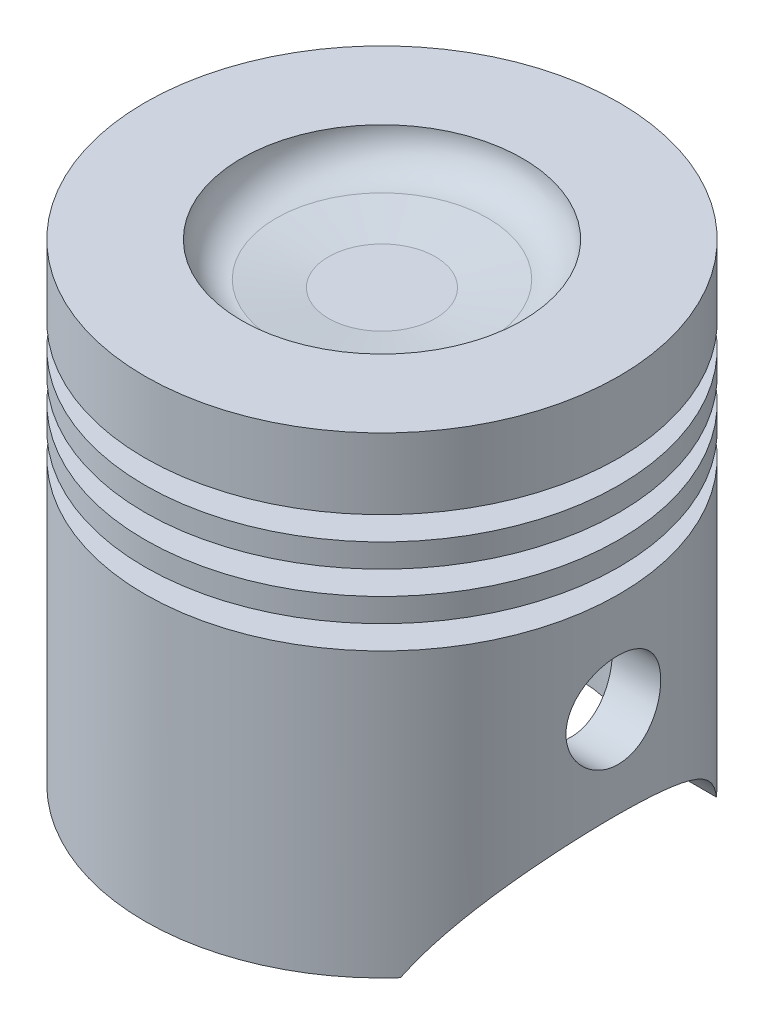
SolidWorks part; units mm, degrees
ref_plane "Front Plane" through (0, 0, 0) normal (0, 0, 1) x (1, 0, 0)
ref_plane "Top Plane" through (0, 0, 0) normal (0, 1, 0) x (1, 0, 0)
ref_plane "Right Plane" through (0, 0, 0) normal (1, 0, 0) x (0, 0, -1)
sketch "Sketch1" plane through (0, 0, 0) normal (0, 0, 1) x (1, 0, 0)
  line L0 (-50.2135, 0) -> (-50.2135, 60)
  line L1 (-50.2135, 60) -> (-43.1425, 60)
  line L2 (-43.1425, 60) -> (-43.1425, 65)
  line L3 (-43.1425, 65) -> (-50.2135, 65)
  line L4 (-50.2135, 65) -> (-50.2135, 70)
  line L5 (-50.2135, 70) -> (-43.1425, 70)
  line L6 (-43.1425, 70) -> (-43.1425, 75)
  line L7 (-43.1425, 75) -> (-50.2135, 75)
  line L8 (-50.2135, 75) -> (-50.2135, 80)
  line L9 (-50.2135, 80) -> (-43.1425, 80)
  line L10 (-43.1425, 80) -> (-43.1425, 85)
  line L11 (-43.1425, 85) -> (-50.2135, 85)
  line L12 (-50.2135, 85) -> (-50.2135, 100)
  line L13 (-50.2135, 100) -> (-29.7582, 100)
  line L14 (-22.4347, 92.6765) -> (-11.3233, 91.1613)
  line L15 (-11.3233, 91.1613) -> (0, 91.1613)
  line L16 (0, 91.1613) -> (0, 0)
  line L17 (0, 0) -> (-50.2135, 0)
  line L18 (0, 116.0419) -> (0, -6.276) construction
  arc A0 (-29.7582, 100) -> (-22.4347, 92.6765) centre (-22.4347, 100) ccw
  point P17 (0, 0)
  dimension "D1" = 100
  dimension "D2" = 5
  dimension "D3" = 5
  dimension "D4" = 5
  dimension "D5" = 5
  dimension "D6" = 5
  dimension "D7" = 15
revolve "Revolve1" add sketch "Sketch1" angle 360 about L18
shell "Shell1" thickness 10 removed face at (0, 0, 50.2135)
sketch "Sketch2" plane through (0, 0, 0) normal (1, 0, 0) x (0, 0, -1)
  line L0 (-50.2135, 0) -> (50.2135, 0) construction
  line L1 (-33.4991, 0) -> (33.0971, 0)
  arc A0 (-33.4991, 0) -> (33.0971, 0) centre (-0.201, -18.2531) cw
  circle A1 centre (-0.201, 38.8783) radius 10
  dimension "D1" = 20
extrude "Cut-Extrude1" cut sketch "Sketch2" against normal blind 60 and the other way blind 60
